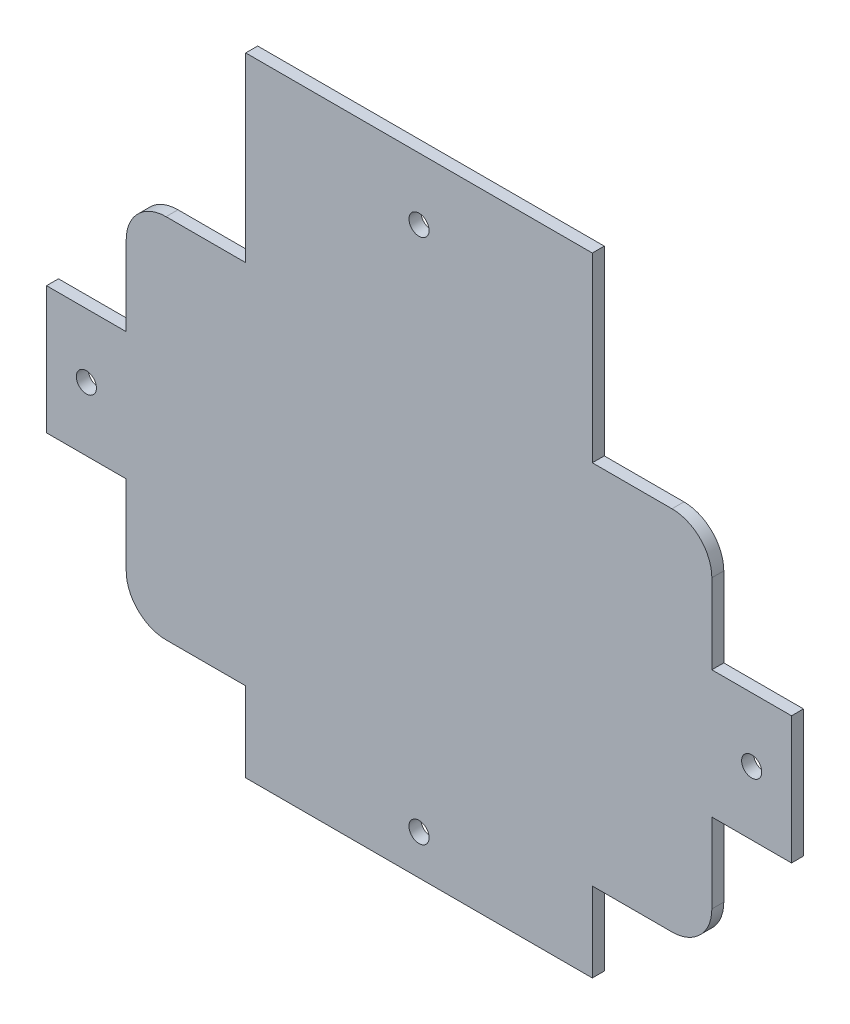
SolidWorks part; units mm, degrees
ref_plane "Front Plane" through (0, 0, 0) normal (0, 0, 1) x (1, 0, 0)
ref_plane "Top Plane" through (0, 0, 0) normal (0, 1, 0) x (1, 0, 0)
ref_plane "Right Plane" through (0, 0, 0) normal (1, 0, 0) x (0, 0, -1)
sketch "Sketch1" plane through (0, 0, 0) normal (0, 0, 1) x (1, 0, 0)
  line L0 (-5.3883, 77.7881) -> (-5.3883, 93.3881) construction
  line L1 (-48.8883, 93.3881) -> (-48.8883, 47.7881)
  line L2 (-48.8883, 47.7881) -> (-68.8883, 47.7881)
  line L3 (-78.8883, 37.7881) -> (-78.8883, 17.7881)
  line L4 (-78.8883, 17.7881) -> (-98.8883, 17.7881)
  line L5 (-98.8883, 17.7881) -> (-98.8883, -14.2119)
  line L6 (-98.8883, 1.7881) -> (-88.8883, 1.7881) construction
  line L7 (-98.8883, -14.2119) -> (-78.8883, -14.2119)
  line L8 (-78.8883, -14.2119) -> (-78.8883, -34.2119)
  line L9 (-68.8883, -44.2119) -> (-48.8883, -44.2119)
  line L10 (-48.8883, -44.2119) -> (-48.8883, -64.2119)
  line L11 (-48.8883, -64.2119) -> (38.1117, -64.2119)
  line L12 (38.1117, -64.2119) -> (38.1117, -44.2119)
  line L13 (38.1117, -44.2119) -> (58.1117, -44.2119)
  line L14 (68.1117, -34.2119) -> (68.1117, -14.2119)
  line L15 (68.1117, -14.2119) -> (88.1117, -14.2119)
  line L16 (78.1117, 1.7881) -> (88.1117, 1.7881) construction
  line L17 (88.1117, -14.2119) -> (88.1117, 17.7881)
  line L18 (88.1117, 17.7881) -> (68.1117, 17.7881)
  line L19 (-5.3883, -64.2119) -> (-5.3883, -54.2119) construction
  line L21 (68.1117, 17.7881) -> (68.1117, 37.7881)
  line L22 (58.1117, 47.7881) -> (38.1117, 47.7881)
  line L23 (38.1117, 47.7881) -> (38.1117, 93.3881)
  line L24 (38.1117, 93.3881) -> (-48.8883, 93.3881)
  arc A0 (68.1117, 37.7881) -> (58.1117, 47.7881) centre (58.1117, 37.7881) ccw
  arc A1 (58.1117, -44.2119) -> (68.1117, -34.2119) centre (58.1117, -34.2119) ccw
  arc A2 (-78.8883, -34.2119) -> (-68.8883, -44.2119) centre (-68.8883, -34.2119) ccw
  arc A3 (-68.8883, 47.7881) -> (-78.8883, 37.7881) centre (-68.8883, 37.7881) ccw
  circle A4 centre (-5.3883, 77.7881) radius 2.525
  circle A5 centre (-88.8883, 1.7881) radius 2.525
  circle A6 centre (78.1117, 1.7881) radius 2.525
  circle A7 centre (-5.3883, -54.2119) radius 2.525
  point P43 (68.1117, 47.7881)
  dimension "D1" = 10
  dimension "D3" = 5.05
  dimension "D2" = 45.6
  dimension "D4" = 10
  dimension "D5" = 15.6
  dimension "D6" = 10
  dimension "D7" = 10
extrude "Boss-Extrude1" add sketch "Sketch1" along normal blind 3
